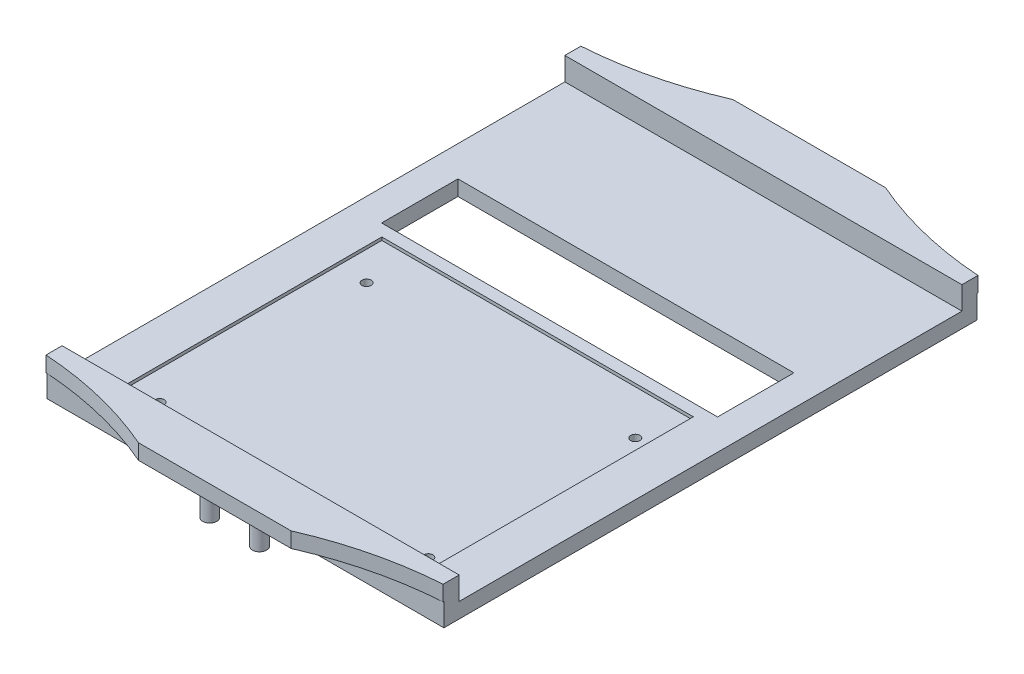
SolidWorks part; units mm, degrees
ref_plane "Front Plane" through (0, 0, 0) normal (0, 0, 1) x (1, 0, 0)
ref_plane "Top Plane" through (0, 0, 0) normal (0, 1, 0) x (1, 0, 0)
ref_plane "Right Plane" through (0, 0, 0) normal (1, 0, 0) x (0, 0, -1)
sketch "Sketch1" plane through (0, 0, 0) normal (1, 0, 0) x (0, 0, -1)
  line L7 (-174.6, 36.382) -> (-174.6, 43.882)
  line L8 (-174.6, 43.882) -> (-184.6, 43.882)
  line L9 (-184.6, 43.882) -> (-184.6, 48.882)
  line L10 (-184.6, 48.882) -> (-169.6, 48.882)
  line L11 (-169.6, 48.882) -> (-169.6, 41.382)
  line L12 (-174.6, 36.382) -> (0, 36.382)
  line L13 (0, 36.382) -> (0, 43.882)
  line L14 (0, 43.882) -> (10, 43.882)
  line L15 (10, 43.882) -> (10, 48.882)
  line L16 (10, 48.882) -> (-5, 48.882)
  line L17 (-5, 48.882) -> (-5, 41.382)
  line L18 (-5, 41.382) -> (-169.6, 41.382)
  dimension "D1" = 194.6
  dimension "D2" = 5
  dimension "D3" = 10
  dimension "D4" = 5
  dimension "D5" = 164.6
  dimension "D6" = 174.6
  dimension "D7" = 2.5
  dimension "D8" = 5
extrude "Boss-Extrude1" add sketch "Sketch1" along normal blind 150
sketch "Sketch2" plane through (0, 0, 0) normal (0, 1, 0) x (1, 0, 0)
  line L2 (50, 10) -> (0, 10)
  line L3 (150, 10) -> (0, 10) construction
  line L9 (100, 10) -> (150, 10)
  line L11 (0, -184.6) -> (50, -184.6)
  line L12 (150, -184.6) -> (0, -184.6) construction
  line L17 (150, -184.6) -> (100, -184.6)
  line L21 (0, 10) -> (0, 0)
  line L22 (0, 0) -> (50, 0)
  line L23 (50, 0) -> (50, 10)
  line L24 (100, 10) -> (100, 0)
  line L25 (100, 0) -> (150, 0)
  line L26 (150, 0) -> (150, 10)
  line L27 (0, -184.6) -> (0, -174.6)
  line L28 (0, -174.6) -> (50, -174.6)
  line L29 (50, -174.6) -> (50, -184.6)
  line L30 (100, -184.6) -> (100, -174.6)
  line L31 (100, -174.6) -> (150, -174.6)
  line L32 (150, -174.6) -> (150, -184.6)
  dimension "D1" = 50
extrude "Cut-Extrude2" cut sketch "Sketch2" along normal up to next
fillet "Fillet1" radius 120 4 edges at (50, 46.382, 174.6) (100, 46.382, 174.6) (100, 46.382, 0) (50, 46.382, 0)
sketch "Sketch4" plane through (0, 48.882, 0) normal (0, 1, 0) x (1, 0, 0)
  line L2 (100, -184.6) -> (50, -184.6) construction
  line L3 (100, 10) -> (50, 10) construction
  circle A0 centre (66.85, -178.1) radius 2.3
  circle A2 centre (83.15, -178.1) radius 2.3
  circle A3 centre (83.15, 3.5) radius 2.3
  circle A4 centre (66.85, 3.5) radius 2.3
  dimension "D2" = 4.6
  dimension "D1" = 16.3
  dimension "D3" = 16.85
  dimension "D4" = 6.5
  dimension "D7" = 6.5
  dimension "D5" = 2
  dimension "D6" = 2
extrude "Boss-Extrude2" add sketch "Sketch4" against normal blind 16
sketch "Sketch7" plane through (0, 32.882, 0) normal (0, -1, 0) x (1, 0, 0)
  circle A0 centre (66.85, 178.1) radius 2.15
  circle A1 centre (83.15, 178.1) radius 2.15
  circle A2 centre (66.85, -3.5) radius 2.15
  circle A3 centre (83.15, -3.5) radius 2.15
  dimension "D1" = 4.3
  dimension "D2" = 4.3
  dimension "D3" = 4.3
  dimension "D4" = 4.3
extrude "Cut-Extrude4" cut sketch "Sketch7" against normal up to surface (11 mm away) up to face at (83.15, 43.882, 180.4)
sketch "Sketch8" plane through (0, 41.382, 0) normal (0, 1, 0) x (1, 0, 0)
  line L0 (20, -75) -> (130, -75)
  line L1 (20, -75) -> (20, -50)
  line L2 (150, -5) -> (0, -5) construction
  line L3 (20, -50) -> (130, -50)
  line L8 (0, -5) -> (0, -169.6) construction
  line L9 (130, -50) -> (130, -75)
  dimension "D1" = 25
  dimension "D2" = 110
  dimension "D3" = 45
  dimension "D4" = 20
extrude "Cut-Extrude5" cut sketch "Sketch8" against normal up to surface (5 mm away) up to face at (75, 36.382, 87.3)
sketch "Sketch10" plane through (0, 41.382, 0) normal (0, 1, 0) x (1, 0, 0)
  line L3 (20, -75) -> (130, -75) construction
  line L12 (25, -78.925) -> (126, -78.925)
  line L13 (126, -78.925) -> (126, -165.6744)
  line L14 (126, -165.6744) -> (24, -165.6744)
  line L15 (24, -165.6744) -> (24, -78.925)
  line L16 (24, -78.925) -> (25, -78.925)
  circle A0 centre (33.5, -93.425) radius 1.5
  circle A1 centre (121.5, -93.425) radius 1.5
  circle A2 centre (121.5, -161.1744) radius 1.5
  circle A3 centre (33.5, -161.1744) radius 1.5
  dimension "D1" = 3
  dimension "D2" = 4.5
  dimension "D3" = 9.5
  dimension "D4" = 4.5
  dimension "D5" = 4.5
  dimension "D7" = 14.5
  dimension "D8" = 14.5
  dimension "D9" = 9.5
  dimension "D10" = 3.925
  dimension "D6" = 4.5
extrude "Cut-Extrude6" cut sketch "Sketch10" against normal blind 1 contours L12 L13 L14 L15 L16
extrude "Cut-Extrude7" cut sketch "Sketch10<3>" against normal through all contours A1 | A0 | A3 | A2
sketch "Sketch10<3>" plane through (0, 41.382, 0) normal (0, 1, 0) x (1, 0, 0) same geometry as "Sketch10"
fillet "Fillet2" radius 1 4 edges at (83.15, 43.882, -1.2) (66.85, 43.882, -1.2) (83.15, 43.882, 180.4) (66.85, 43.882, 180.4)
sketch "Sketch11" plane through (0, 41.382, 0) normal (0, 1, 0) x (1, 0, 0)
  line L0 (10, 10) -> (0, 10)
  line L1 (10, -184.6) -> (0, -184.6)
  line L2 (0, 10) -> (0, -184.6)
  line L3 (140, 10) -> (150, 10)
  line L4 (10, 10) -> (10, -184.6)
  line L6 (150, 10) -> (150, -184.6)
  line L8 (140, 10) -> (140, -184.6)
  line L9 (140, -184.6) -> (150, -184.6)
extrude "Cut-Extrude8" cut sketch "Sketch11" along normal through all both and the other way through all
